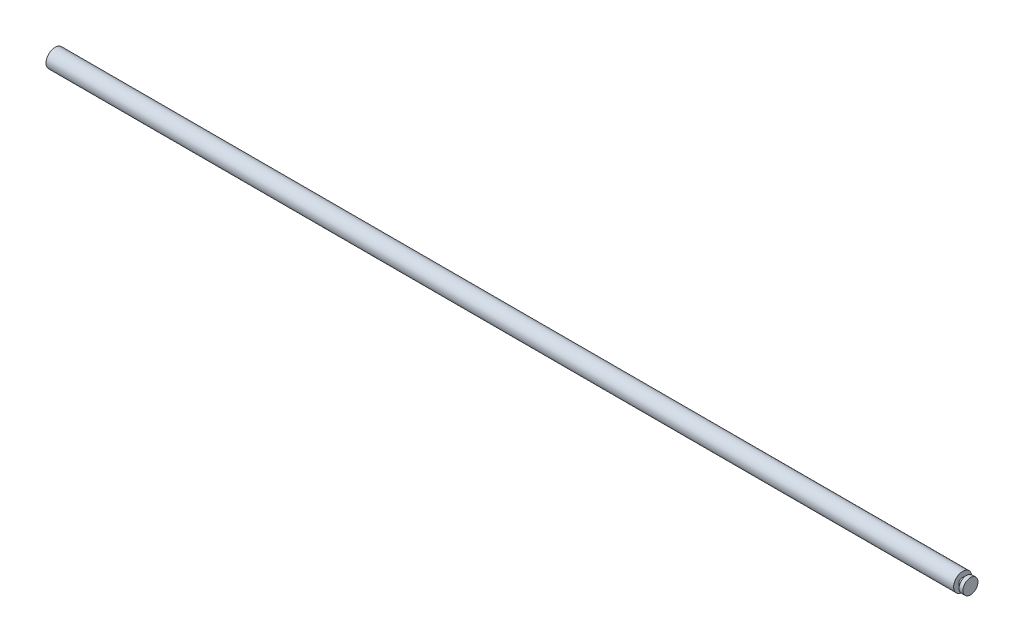
SolidWorks part; units mm, degrees
ref_plane "Front Plane" through (0, 0, 0) normal (0, 0, 1) x (1, 0, 0)
ref_plane "Top Plane" through (0, 0, 0) normal (0, 1, 0) x (1, 0, 0)
ref_plane "Right Plane" through (0, 0, 0) normal (1, 0, 0) x (0, 0, -1)
sketch "Sketch1" plane through (0, 0, 0) normal (0, 0, 1) x (1, 0, 0)
  line L0 (0, 34.9364) -> (0, -34.4273) construction
  line L1 (-72.6727, 0) -> (73.8182, 0) construction
  line L2 (173.5, 6.5441) -> (173.5, -8.583) construction
  line L3 (-176.5, 0) -> (176.5, 0)
  line L4 (-176.5, 0) -> (-176.5, 3.5)
  line L5 (-176.5, 3.5) -> (173.5, 3.5)
  line L6 (176.5, 0) -> (176.5, 2.9)
  line L7 (173.5, 3.5) -> (173.5, 1.5)
  line L8 (173.5, 1.5) -> (175, 1.5)
  line L9 (175, 1.5) -> (175, 2.9)
  line L10 (175, 2.9) -> (176.5, 2.9)
  dimension "D1" = 3.5
  dimension "D2" = 353
  dimension "D3" = 3
  dimension "D4" = 2
  dimension "D5" = 1.5
  dimension "D6" = 1.4
revolve "Revolve2" add sketch "Sketch1" angle 360 about L3
